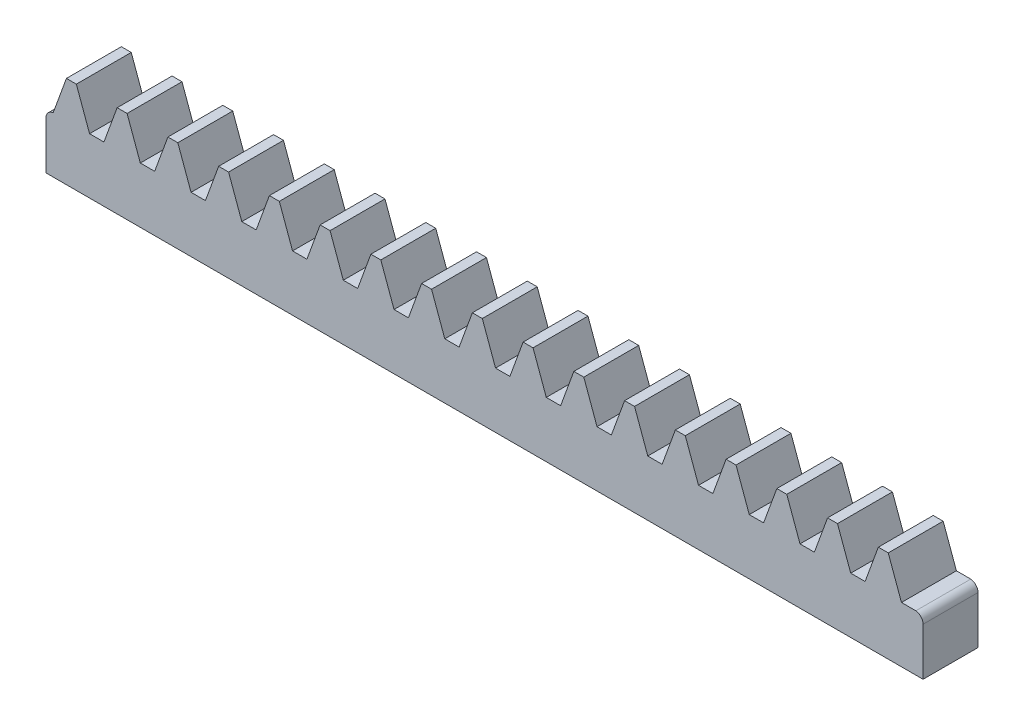
SolidWorks part; units mm, degrees
extrude "Blank" add sketch "BlankSke" against normal blind 3.4
sketch "BlankSke" plane through (0, 0, 0) normal (0, 0, 1) x (1, 0, 0)
  line L1 (0, 0) -> (54.3, 0)
  line L2 (0, 0) -> (0, 5.7)
  line L3 (0, 5.7) -> (54.3, 5.7)
  line L4 (54.3, 0) -> (54.3, 5.7)
  dimension "Length" = 54.3
ref_plane "Plane1" through (0, 0, 0) normal (0, 0, 1) x (1, 0, 0)
ref_plane "Plane2" through (0, 0, 0) normal (0, 1, 0) x (1, 0, 0)
ref_plane "Plane3" through (0, 0, 0) normal (1, 0, 0) x (0, 0, -1)
sketch "HoldingSke" plane through (0, 0, 0) normal (0, 1, 0) x (1, 0, 0)
  line L0 (0, 0) -> (0.1392, 0.9903)
  line L1 (-15, 0) -> (100, 0) construction
  line L2 (0, 0) -> (-2.1039, 2.3779)
  line L3 (0, 0) -> (-11.863, 4.5341)
  line L4 (0, 0) -> (8.1655, 2.8116)
  line L5 (0, 0) -> (-23.7986, -8.8762)
  line L6 (0, 0) -> (-10.5278, -7.1032)
  line L9 (-71.009, 38.7566) -> (-19.9837, 57.3283)
  line L10 (-76.2, 3.3779) -> (-71.5, 3.3779)
  line L11 (0, 0) -> (-3.4, 0)
  line L12 (-76.2, 101.6) -> (-76.162, 101.6)
  line L13 (24.9733, 27.94) -> (52.9518, 28.4284)
  line L14 (24.9733, 27.94) -> (24.9743, 27.94)
  line L15 (24.9733, 27.94) -> (100.4006, 29.5858)
  circle A0 centre (0, 0) radius 19.05
  circle A1 centre (0, 0) radius 2.35
  circle A2 centre (0, 0) radius 12.7
  dimension "Num_teeth" = 19
  dimension "Width" = 3.4
  dimension "Length" = 54.3
  dimension "Pitch_height" = 4.7
sketch "TooCutSkeIll" plane through (0, 0, 0) normal (0, 0, 1) x (1, 0, 0)
  line L0 (-1.2538, 5.6737) -> (-0.5045, 3.6152)
  line L1 (-0.2687, 3.45) -> (0.2687, 3.45)
  line L2 (0.5045, 3.6152) -> (1.2538, 5.6737)
  line L3 (54.3, 5.7) -> (0, 5.7) construction
  line L4 (0, 0) -> (0, 64.897) construction
  line L5 (-13.208, 4.7) -> (12.954, 4.7) construction
  line L6 (0, 0) -> (54.3, 0) construction
  line L7 (0.8994, 4.7) -> (0.8994, 48.7463) construction
  line L8 (-0.8994, 4.7) -> (-0.8994, 48.7463) construction
  line L9 (1.2914, 5.7) -> (1.2914, 5.7254)
  line L10 (-1.2914, 5.7) -> (-1.2914, 5.7254)
  line L11 (-1.2914, 5.7254) -> (1.2914, 5.7254)
  arc A0 (0.2687, 3.45) -> (0.5045, 3.6152) centre (0.2687, 3.701) ccw
  arc A1 (-0.5045, 3.6152) -> (-0.2687, 3.45) centre (-0.2687, 3.701) ccw
  arc A2 (1.2914, 5.7) -> (1.2538, 5.6737) centre (1.2914, 5.66) ccw
  arc A3 (-1.2538, 5.6737) -> (-1.2914, 5.7) centre (-1.2914, 5.66) ccw
  dimension "Addendum_plus" = 1.0254
  dimension "Pitch_height" = 4.7
  dimension "Pressure_angle" = 20
  dimension "Gap_width" = 1.7988
  dimension "Dedendum" = 1.25
extrude "ToothCutIll" [suppressed] cut sketch "TooCutSkeIll" against normal through all
sketch "TooCutSkeSim" plane through (0, 0, 0) normal (0, 0, 1) x (1, 0, 0)
  line L0 (0.4444, 3.45) -> (-0.4444, 3.45)
  line L1 (1.2726, 5.7254) -> (0.4444, 3.45)
  line L2 (0, 17.4625) -> (0, 53.467) construction
  line L3 (1.2726, 5.7254) -> (-1.2726, 5.7254)
  line L6 (-1.2726, 5.7254) -> (-0.4444, 3.45)
  line L9 (-0.8994, 4.7) -> (0.8994, 4.7) construction
  line L10 (0, 0) -> (54.3, 0) construction
  line L11 (0.8994, 4.7) -> (0.8994, 53.467) construction
  line L12 (-0.8994, 4.7) -> (-0.8994, 53.467) construction
  dimension "Addendum_plus" = 1.0254
  dimension "Pitch_height" = 4.7
  dimension "Pressure_angle" = 20
  dimension "Gap_width" = 1.7988
  dimension "Dedendum" = 1.25
extrude "ToothCutSim" cut sketch "TooCutSkeSim" against normal through all
pattern_linear "TeethCuts" count 19 spacing 3.1416 along (1, 0, 0) of "ToothCutIll", "ToothCutSim"
fillet "Verrundung1" radius 0.5 1 edges at (54.3, 4.6822, -1.7)
fillet "Verrundung2" radius 0.5 1 edges at (0, 3.45, -1.7)
equation "' \"Module@HoldingSke\" = 6.35"
equation "' \"Num_teeth@HoldingSke\" = 12"
equation "' \"Ap@HoldingSke\" =  20"
equation "' \"Ap@HoldingSke\" = 20"
equation "' \"Width@HoldingSke\" = 0.25 * 25.4"
equation "' \"Show_teeth@HoldingSke\" = 500"
equation "' \"Backlash@HoldingSke\" = 0.009 * 25.4"
equation "' \"Addendum_fac@HoldingSke\" = 1.0"
equation "' \"Dedendum_fac@HoldingSke\" = 1.25"
equation "' \"Dedendum_add@HoldingSke\" = 0.00005 * 25.4"
equation "' \"Clearance_fac@HoldingSke\" = 0.25"
equation "' \"Pitch_height@HoldingSke\" = 1 * 25.4"
equation "' \"Length@HoldingSke\" = 4.71 * 25.4"
equation "\"Pitch@HoldingSke\" = 1 / \"Module@HoldingSke\""
equation "\"MPH@HoldingSke\" = \"Dedendum_fac@HoldingSke\" / \"Pitch@HoldingSke\" + 2 * \"Dedendum_add@HoldingSke\" + 0.002 * 25.4"
equation "\"MPH@HoldingSke\" = ((sgn( \"MPH@HoldingSke\" - \"Pitch_height@HoldingSke\")+1)*( \"MPH@HoldingSke\" - \"Pitch_height@HoldingSke\"))/2 + \"Pitch_height@HoldingSke\""
equation "\"Blank_height@BlankSke\" = \"Pitch_height@HoldingSke\" + \"Addendum_fac@HoldingSke\"  / \"Pitch@HoldingSke\" "
equation "\"Length@BlankSke\" =  \"Length@HoldingSke\""
equation "\"Face_width@Blank\" = \"Width@HoldingSke\""
equation "\"Pressure_angle@TooCutSkeIll\" = \"Ap@HoldingSke\""
equation "\"Addendum_plus@TooCutSkeIll\" =  \"Addendum_fac@HoldingSke\"  / \"Pitch@HoldingSke\" + 0.001 *25.4"
equation "\"Dedendum@TooCutSkeIll\" = \"Dedendum_fac@HoldingSke\"  / \"Pitch@HoldingSke\""
equation "\"Pitch_height@TooCutSkeIll\" =  \"MPH@HoldingSke\""
equation "\"Gap_width@TooCutSkeIll\" = 3.14159265 / 2 / \"Pitch@HoldingSke\" + 6 * \"Backlash@HoldingSke\""
equation "\"Pressure_angle@TooCutSkeSim\" = \"Ap@HoldingSke\""
equation "\"Addendum_plus@TooCutSkeSim\" =  \"Addendum_fac@HoldingSke\"  / \"Pitch@HoldingSke\" + 0.001 * 25.4"
equation "\"Dedendum@TooCutSkeSim\" = \"Dedendum_fac@HoldingSke\"  / \"Pitch@HoldingSke\""
equation "\"Pitch_height@TooCutSkeSim\" =  \"MPH@HoldingSke\""
equation "\"Gap_width@TooCutSkeSim\" = 3.14159265 / 2 / \"Pitch@HoldingSke\" + 6 * \"Backlash@HoldingSke\""
equation "\"Root_fillet@TooCutSkeIll\" = \"Clearance_fac@HoldingSke\" / \"Pitch@HoldingSke\" + \"Dedendum_add@HoldingSke\""
equation "\"Break_rad@TooCutSkeIll\" = 0.02 / \"Pitch@HoldingSke\" * 2"
equation "\"Linear_pitch@TeethCuts\" = 3.14159265 / \"Pitch@HoldingSke\""
equation "\"Num_teeth@HoldingSke\" = int( ( \"Length@HoldingSke\" + 0 ) / (3.14159265 / \"Pitch@HoldingSke\")) + 0.9999  + 1"
equation " \"Num_teeth@TeethCuts\" = int( \"Show_teeth@HoldingSke\" ) + 1"
equation " \"Num_teeth@TeethCuts\" = ((sgn( \"Num_teeth@TeethCuts\" - \"Num_teeth@HoldingSke\" )-1)*( \"Num_teeth@TeethCuts\" - \"Num_teeth@HoldingSke\" ))/-2+ \"Num_teeth@HoldingSke\""
equation " \"Num_teeth@TeethCuts\" = ((sgn( \"Num_teeth@TeethCuts\" - 2.0)+1)*( \"Num_teeth@TeethCuts\" - 2.0))/2 +2.0"
